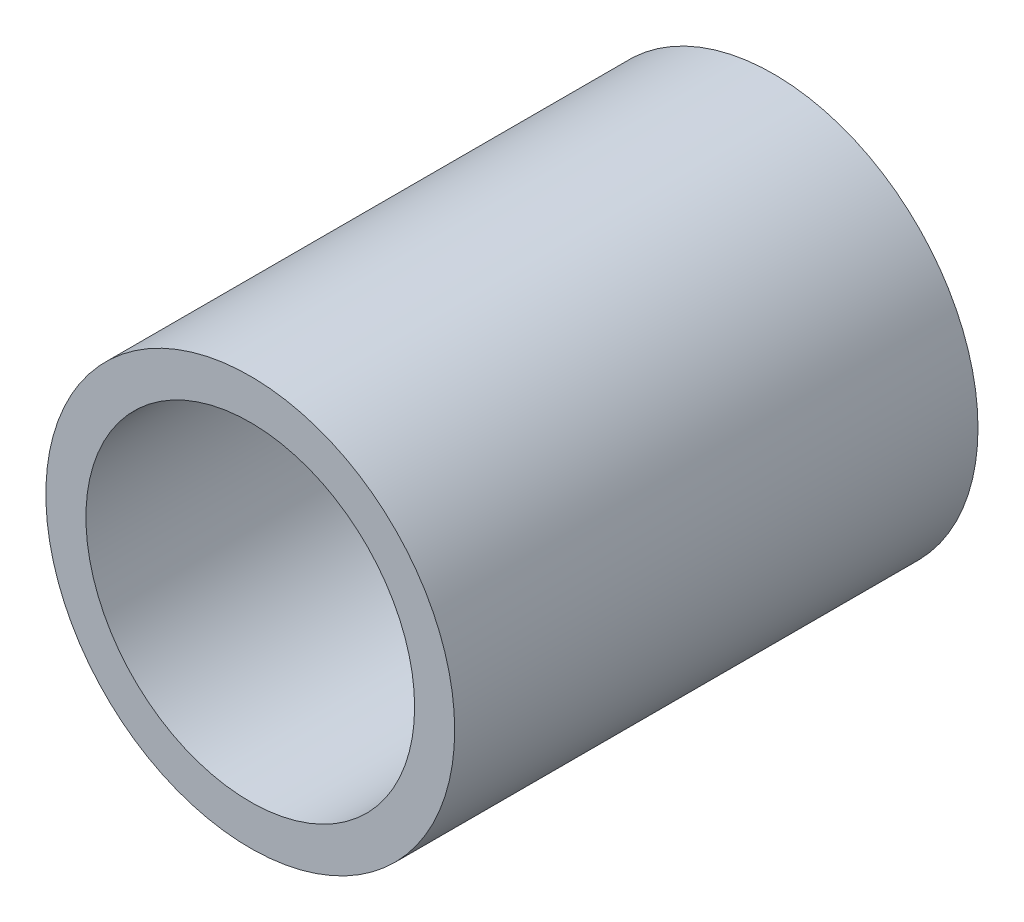
SolidWorks part; units mm, degrees
ref_plane "Front Plane" through (0, 0, 0) normal (0, 0, 1) x (1, 0, 0)
ref_plane "Top Plane" through (0, 0, 0) normal (0, 1, 0) x (1, 0, 0)
ref_plane "Right Plane" through (0, 0, 0) normal (1, 0, 0) x (0, 0, -1)
sketch "Sketch1" plane through (0, 0, 0) normal (0, 0, 1) x (1, 0, 0)
  line L0 (6.35, 0) -> (-6.35, 0) construction
  line L1 (0, -5.1054) -> (0, 5.1054) construction
  line L2 (0, -6.35) -> (0, 6.35) construction
  circle A0 centre (0, 0) radius 6.35 construction
  circle A1 centre (0, 0) radius 5.1054 construction
  point P6 (0, 0)
  point P7 (-5.1054, 0)
  point P8 (5.1054, 0)
  point P10 (-6.35, 0)
  point P11 (6.35, 0)
  point P14 (0, 0)
  point P17 (0, 0)
  point P18 (0, 5.1054)
  point P19 (0, 6.35)
  point P20 (0, -5.1054)
  point P21 (0, -6.35)
  dimension "OD" = 12.7
  dimension "ID" = 10.2108
  dimension "Wall Thickness" = 1.2446
sketch "Sketch2" plane through (0, 0, 0) normal (1, 0, 0) x (0, 0, -1)
  line L0 (0, -5.1054) -> (0, 5.1054) construction
  line L1 (0, -5.1054) -> (0, 5.1054) construction
  line L2 (0, -6.35) -> (0, 6.35) construction
  line L3 (0, -6.35) -> (0, 6.35) construction
  line L4 (8.128, 6.35) -> (-8.128, 6.35) construction
  line L5 (8.128, 5.1054) -> (-8.128, 5.1054) construction
  line L6 (8.128, -5.1054) -> (-8.128, -5.1054) construction
  line L7 (8.128, -6.35) -> (-8.128, -6.35) construction
  line L8 (-8.128, -6.35) -> (-8.128, 6.35) construction
  line L9 (8.128, 6.35) -> (8.128, -6.35) construction
  line L10 (8.128, 0) -> (-8.128, 0) construction
  line L11 (-2.4836, -6.35) -> (-2.4836, 6.35) construction
  line L12 (2.4836, -6.35) -> (2.4836, 6.35) construction
  point P7 (0, 6.35)
  point P10 (0, 5.1054)
  point P13 (0, -5.1054)
  point P16 (0, -6.35)
  point P17 (-8.128, -6.35)
  point P18 (-8.128, -5.1054)
  point P19 (-8.128, 5.1054)
  point P20 (-8.128, 6.35)
  point P21 (8.128, 6.35)
  point P22 (8.128, 5.1054)
  point P23 (8.128, -5.1054)
  point P24 (8.128, -6.35)
  point P28 (0, 0)
  point P30 (-2.4836, 0)
  point P31 (-2.4836, -6.35)
  point P32 (-2.4836, 6.35)
  point P35 (2.4836, 0)
  point P36 (2.4836, 6.35)
  point P37 (2.4836, -6.35)
  dimension "Length" = 16.256
  dimension "Break Line" = 5.6444
sketch "Sketch3" plane through (0, 0, 0) normal (0, 0, 1) x (1, 0, 0)
  circle A0 centre (0, 0) radius 5.1054 construction
  circle A1 centre (0, 0) radius 6.35 construction
  circle A2 centre (0, 0) radius 5.1054
  circle A3 centre (0, 0) radius 6.35
extrude "Boss-Extrude1" add sketch "Sketch3" along normal up to vertex (8.128 mm away) and the other way up to vertex (8.128 mm away) up to point (0, 0, 8.128) other way up to point (0, 0, -8.128)
equation "\"Break Line@Sketch2\"=\"OD@Sketch1\"/2.25"
